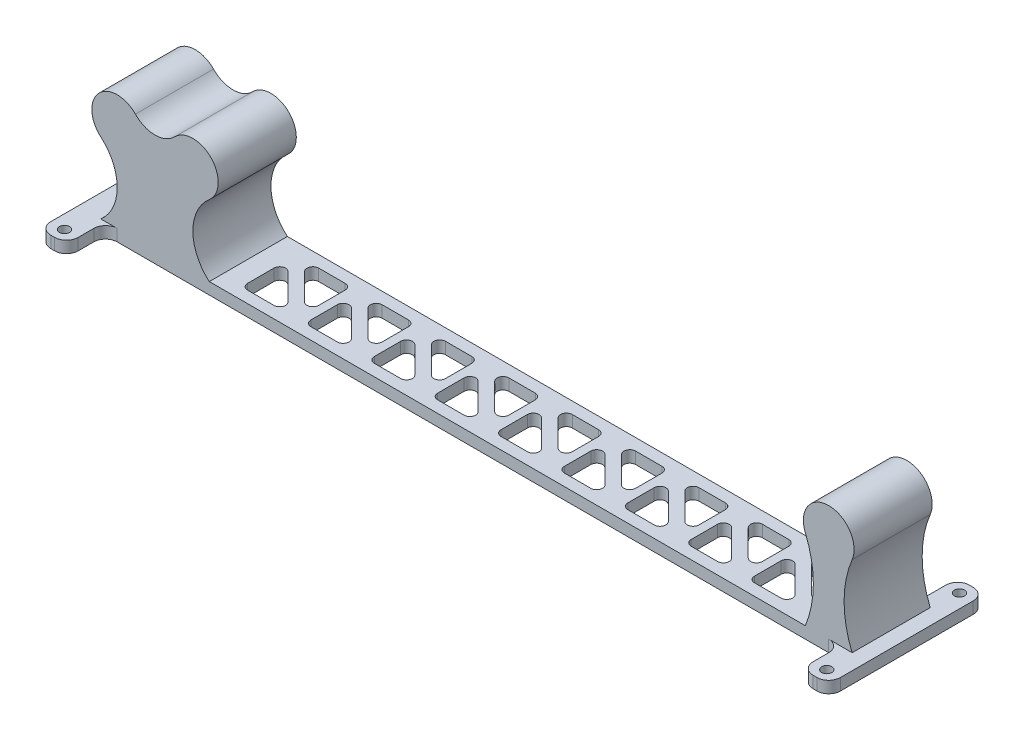
SolidWorks part; units mm, degrees
ref_plane "Front Plane" through (0, 0, 0) normal (0, 0, 1) x (1, 0, 0)
ref_plane "Top Plane" through (0, 0, 0) normal (0, 1, 0) x (1, 0, 0)
ref_plane "Right Plane" through (0, 0, 0) normal (1, 0, 0) x (0, 0, -1)
sketch "Sketch1" plane through (0, 0, 0) normal (0, 0, 1) x (1, 0, 0)
  line L0 (4.2086, -23.15) -> (156.86, -23.15)
  line L1 (-19.38, 0) -> (0, 0) construction
  line L2 (-9.69, 0) -> (-9.69, -23.15) construction
  line L3 (-23.5886, -4.9535) -> (-23.5886, -23.15) construction
  line L4 (-19.38, -14.0518) -> (-19.38, 0) construction
  line L5 (162.86, 0) -> (162.86, -23.15) construction
  line L6 (168.86, -2.5) -> (168.86, -23.15) construction
  line L7 (-29.38, -23.15) -> (-29.38, -26.15)
  line L8 (-29.38, -26.15) -> (172.86, -26.15)
  line L9 (172.86, -26.15) -> (172.86, -23.15)
  line L10 (-23.5886, -23.15) -> (-29.38, -23.15)
  line L11 (168.86, -23.15) -> (172.86, -23.15)
  circle A0 centre (0, 0) radius 3.3734
  circle A1 centre (-19.38, 0) radius 3.3734
  circle A2 centre (162.86, 0) radius 3.3734
  arc A3 (-14.7144, 4.5258) -> (-23.5886, -4.9535) centre (-19.38, 0) ccw
  arc A4 (4.2086, -4.9535) -> (-4.6656, 4.5258) centre (0, 0) ccw
  arc A5 (-23.5886, -4.9535) -> (-23.5886, -23.15) centre (-31.3186, -14.0518) cw
  arc A6 (-14.7144, 4.5258) -> (-4.6656, 4.5258) centre (-9.69, 9.3997) ccw
  arc A7 (4.2086, -4.9535) -> (4.2086, -23.15) centre (11.9386, -14.0518) ccw
  arc A8 (168.86, -2.5) -> (156.86, -2.5) centre (162.86, 0) ccw
  arc A9 (168.86, -2.5) -> (168.86, -23.15) centre (193.64, -12.825) ccw
  arc A10 (156.86, -2.5) -> (156.86, -23.15) centre (132.08, -12.825) cw
  dimension "D1" = 6.7469
  dimension "D7" = 13
  dimension "D8" = 7
  dimension "D2" = 19.38
  dimension "D3" = 162.86
  dimension "D4" = 10
  dimension "D5" = 10
  dimension "D6" = 3
  dimension "D9" = 6
  dimension "D10" = 26.15
extrude "Boss-Extrude1" add sketch "Sketch1" along normal blind 20 contours A0 | A1 | A2 | A8 A10 L0 A7 A4 A6 A3 A5 L10 L7 L8 L9 L11 A9 region at (0, 0, 0) region at (-19.38, 0, 0) region at (162.86, 0, 0)
extrude "Boss-Extrude2" add sketch "Sketch1<3>" against normal blind 3 from surface contours A8 A10 L0 A7 A4 A6 A3 A5 L10 L7 L8 L9 L11 A9 A0 A1 A2 | A0 | A1 | A2 region at (80.5343, -25.1986, 0) region at (0, 0, 0) region at (-19.38, 0, 0) region at (162.86, 0, 0) starting at face at (-16.0066, 0, 20)
sketch "Sketch1<3>" plane through (0, 0, 0) normal (0, 0, 1) x (1, 0, 0) same geometry as "Sketch1"
sketch "Sketch2" plane through (0, -23.15, 0) normal (0, 1, 0) x (1, 0, 0)
  line L0 (6.5, 0) -> (26.5, -20) construction
  line L1 (4.2086, -20) -> (156.86, -20) construction
  line L2 (9.5, -8.7426) -> (9.5, -15.5)
  line L3 (11, -17) -> (17.7574, -17)
  line L4 (18.818, -14.4393) -> (12.0607, -7.682)
  line L5 (6.5, -20) -> (6.5, 0) construction
  line L6 (23.5, -4.5) -> (23.5, -11.2574)
  line L7 (15.2426, -3) -> (22, -3)
  line L8 (20.9393, -12.318) -> (14.182, -5.5607)
  line L9 (35.0505, -14.4393) -> (28.2932, -7.682)
  line L10 (25.7325, -8.7426) -> (25.7325, -15.5)
  line L11 (27.2325, -17) -> (33.9899, -17)
  line L12 (39.7325, -4.5) -> (39.7325, -11.2574)
  line L13 (37.1718, -12.318) -> (30.4145, -5.5607)
  line L14 (31.4751, -3) -> (38.2325, -3)
  line L15 (51.283, -14.4393) -> (44.5257, -7.682)
  line L16 (41.965, -8.7426) -> (41.965, -15.5)
  line L17 (43.465, -17) -> (50.2224, -17)
  line L18 (55.965, -4.5) -> (55.965, -11.2574)
  line L19 (53.4043, -12.318) -> (46.647, -5.5607)
  line L20 (47.7076, -3) -> (54.465, -3)
  line L21 (67.5155, -14.4393) -> (60.7582, -7.682)
  line L22 (58.1975, -8.7426) -> (58.1975, -15.5)
  line L23 (59.6975, -17) -> (66.4549, -17)
  line L24 (72.1975, -4.5) -> (72.1975, -11.2574)
  line L25 (69.6368, -12.318) -> (62.8795, -5.5607)
  line L26 (63.9401, -3) -> (70.6975, -3)
  line L27 (83.748, -14.4393) -> (76.9907, -7.682)
  line L28 (74.43, -8.7426) -> (74.43, -15.5)
  line L29 (75.93, -17) -> (82.6874, -17)
  line L30 (88.43, -4.5) -> (88.43, -11.2574)
  line L31 (85.8693, -12.318) -> (79.112, -5.5607)
  line L32 (80.1726, -3) -> (86.93, -3)
  line L33 (99.9805, -14.4393) -> (93.2232, -7.682)
  line L34 (90.6625, -8.7426) -> (90.6625, -15.5)
  line L35 (92.1625, -17) -> (98.9199, -17)
  line L36 (104.6625, -4.5) -> (104.6625, -11.2574)
  line L37 (102.1018, -12.318) -> (95.3445, -5.5607)
  line L38 (96.4051, -3) -> (103.1625, -3)
  line L39 (116.213, -14.4393) -> (109.4557, -7.682)
  line L40 (106.895, -8.7426) -> (106.895, -15.5)
  line L41 (108.395, -17) -> (115.1524, -17)
  line L42 (120.895, -4.5) -> (120.895, -11.2574)
  line L43 (118.3343, -12.318) -> (111.577, -5.5607)
  line L44 (112.6376, -3) -> (119.395, -3)
  line L45 (132.4455, -14.4393) -> (125.6882, -7.682)
  line L46 (123.1275, -8.7426) -> (123.1275, -15.5)
  line L47 (124.6275, -17) -> (131.3849, -17)
  line L48 (137.1275, -4.5) -> (137.1275, -11.2574)
  line L49 (134.5668, -12.318) -> (127.8095, -5.5607)
  line L50 (128.8701, -3) -> (135.6275, -3)
  line L51 (148.678, -14.4393) -> (141.9207, -7.682)
  line L52 (139.36, -8.7426) -> (139.36, -15.5)
  line L53 (140.86, -17) -> (147.6174, -17)
  line L54 (153.36, -4.5) -> (153.36, -11.2574)
  line L55 (150.7993, -12.318) -> (144.042, -5.5607)
  line L56 (145.1026, -3) -> (151.86, -3)
  line L57 (156.36, 0) -> (156.36, -20) construction
  arc A0 (18.818, -14.4393) -> (17.7574, -17) centre (17.7574, -15.5) cw
  arc A1 (9.5, -8.7426) -> (12.0607, -7.682) centre (11, -8.7426) cw
  arc A2 (9.5, -15.5) -> (11, -17) centre (11, -15.5) ccw
  arc A3 (15.2426, -3) -> (14.182, -5.5607) centre (15.2426, -4.5) ccw
  arc A4 (23.5, -11.2574) -> (20.9393, -12.318) centre (22, -11.2574) cw
  arc A5 (22, -3) -> (23.5, -4.5) centre (22, -4.5) cw
  arc A6 (25.7325, -8.7426) -> (28.2932, -7.682) centre (27.2325, -8.7426) cw
  arc A7 (35.0505, -14.4393) -> (33.9899, -17) centre (33.9899, -15.5) cw
  arc A8 (25.7325, -15.5) -> (27.2325, -17) centre (27.2325, -15.5) ccw
  arc A9 (38.2325, -3) -> (39.7325, -4.5) centre (38.2325, -4.5) cw
  arc A10 (39.7325, -11.2574) -> (37.1718, -12.318) centre (38.2325, -11.2574) cw
  arc A11 (31.4751, -3) -> (30.4145, -5.5607) centre (31.4751, -4.5) ccw
  arc A12 (41.965, -8.7426) -> (44.5257, -7.682) centre (43.465, -8.7426) cw
  arc A13 (51.283, -14.4393) -> (50.2224, -17) centre (50.2224, -15.5) cw
  arc A14 (41.965, -15.5) -> (43.465, -17) centre (43.465, -15.5) ccw
  arc A15 (54.465, -3) -> (55.965, -4.5) centre (54.465, -4.5) cw
  arc A16 (55.965, -11.2574) -> (53.4043, -12.318) centre (54.465, -11.2574) cw
  arc A17 (47.7076, -3) -> (46.647, -5.5607) centre (47.7076, -4.5) ccw
  arc A18 (58.1975, -8.7426) -> (60.7582, -7.682) centre (59.6975, -8.7426) cw
  arc A19 (67.5155, -14.4393) -> (66.4549, -17) centre (66.4549, -15.5) cw
  arc A20 (58.1975, -15.5) -> (59.6975, -17) centre (59.6975, -15.5) ccw
  arc A21 (70.6975, -3) -> (72.1975, -4.5) centre (70.6975, -4.5) cw
  arc A22 (72.1975, -11.2574) -> (69.6368, -12.318) centre (70.6975, -11.2574) cw
  arc A23 (63.9401, -3) -> (62.8795, -5.5607) centre (63.9401, -4.5) ccw
  arc A24 (74.43, -8.7426) -> (76.9907, -7.682) centre (75.93, -8.7426) cw
  arc A25 (83.748, -14.4393) -> (82.6874, -17) centre (82.6874, -15.5) cw
  arc A26 (74.43, -15.5) -> (75.93, -17) centre (75.93, -15.5) ccw
  arc A27 (86.93, -3) -> (88.43, -4.5) centre (86.93, -4.5) cw
  arc A28 (88.43, -11.2574) -> (85.8693, -12.318) centre (86.93, -11.2574) cw
  arc A29 (80.1726, -3) -> (79.112, -5.5607) centre (80.1726, -4.5) ccw
  arc A30 (90.6625, -8.7426) -> (93.2232, -7.682) centre (92.1625, -8.7426) cw
  arc A31 (99.9805, -14.4393) -> (98.9199, -17) centre (98.9199, -15.5) cw
  arc A32 (90.6625, -15.5) -> (92.1625, -17) centre (92.1625, -15.5) ccw
  arc A33 (103.1625, -3) -> (104.6625, -4.5) centre (103.1625, -4.5) cw
  arc A34 (104.6625, -11.2574) -> (102.1018, -12.318) centre (103.1625, -11.2574) cw
  arc A35 (96.4051, -3) -> (95.3445, -5.5607) centre (96.4051, -4.5) ccw
  arc A36 (106.895, -8.7426) -> (109.4557, -7.682) centre (108.395, -8.7426) cw
  arc A37 (116.213, -14.4393) -> (115.1524, -17) centre (115.1524, -15.5) cw
  arc A38 (106.895, -15.5) -> (108.395, -17) centre (108.395, -15.5) ccw
  arc A39 (119.395, -3) -> (120.895, -4.5) centre (119.395, -4.5) cw
  arc A40 (120.895, -11.2574) -> (118.3343, -12.318) centre (119.395, -11.2574) cw
  arc A41 (112.6376, -3) -> (111.577, -5.5607) centre (112.6376, -4.5) ccw
  arc A42 (123.1275, -8.7426) -> (125.6882, -7.682) centre (124.6275, -8.7426) cw
  arc A43 (132.4455, -14.4393) -> (131.3849, -17) centre (131.3849, -15.5) cw
  arc A44 (123.1275, -15.5) -> (124.6275, -17) centre (124.6275, -15.5) ccw
  arc A45 (135.6275, -3) -> (137.1275, -4.5) centre (135.6275, -4.5) cw
  arc A46 (137.1275, -11.2574) -> (134.5668, -12.318) centre (135.6275, -11.2574) cw
  arc A47 (128.8701, -3) -> (127.8095, -5.5607) centre (128.8701, -4.5) ccw
  arc A48 (139.36, -8.7426) -> (141.9207, -7.682) centre (140.86, -8.7426) cw
  arc A49 (148.678, -14.4393) -> (147.6174, -17) centre (147.6174, -15.5) cw
  arc A50 (139.36, -15.5) -> (140.86, -17) centre (140.86, -15.5) ccw
  arc A51 (151.86, -3) -> (153.36, -4.5) centre (151.86, -4.5) cw
  arc A52 (153.36, -11.2574) -> (150.7993, -12.318) centre (151.86, -11.2574) cw
  arc A53 (145.1026, -3) -> (144.042, -5.5607) centre (145.1026, -4.5) ccw
  point P15 (21.3787, -17)
  point P18 (9.5, -5.1213)
  point P21 (9.5, -17)
  point P24 (11.6213, -3)
  point P27 (23.5, -14.8787)
  point P30 (23.5, -3)
  dimension "D5" = 1.5
  dimension "D1" = 45
  dimension "D2" = 3
  dimension "D3" = 3
  dimension "D4" = 3
  dimension "D7" = 3
  dimension "D6" = 9
extrude "Cut-Extrude1" cut sketch "Sketch2" against normal through all
sketch "Sketch3" plane through (0, -23.15, 0) normal (0, 1, 0) x (1, 0, 0)
  line L0 (-25.88, 7) -> (-25.88, 10) construction
  line L1 (-29.38, 0) -> (-22.38, 0)
  line L2 (-29.38, 0) -> (-29.38, 10)
  line L3 (-29.38, 10) -> (-22.38, 10)
  line L4 (-22.38, 0) -> (-22.38, 10)
  line L5 (-29.38, -10) -> (172.86, -10) construction
  line L6 (-29.38, -20) -> (-29.38, 0) construction
  line L7 (172.86, -20) -> (172.86, 0) construction
  line L8 (71.74, -10) -> (71.74, -20) construction
  line L9 (4.2086, -20) -> (156.86, -20) construction
  line L10 (-29.38, 0) -> (-29.38, 10)
  line L11 (-22.38, 0) -> (-22.38, 10)
  line L12 (-29.38, 0) -> (-29.38, 10)
  line L13 (-22.38, 0) -> (-22.38, 10)
  line L14 (-29.38, 0) -> (-29.38, 10)
  line L15 (-22.38, 0) -> (-22.38, 10)
  line L16 (-29.38, -30) -> (-22.38, -30)
  line L17 (-22.38, -20) -> (-22.38, -30)
  line L18 (-29.38, -20) -> (-22.38, -20)
  line L19 (-29.38, -20) -> (-29.38, -30)
  line L20 (-22.38, -20) -> (-22.38, -30)
  line L21 (-29.38, -20) -> (-29.38, -30)
  line L22 (-29.38, 0) -> (-29.38, 10)
  line L23 (-22.38, 0) -> (-22.38, 10)
  line L24 (-29.38, 0) -> (-29.38, 10)
  line L25 (-22.38, 0) -> (-22.38, 10)
  line L26 (-29.38, 0) -> (-29.38, 10)
  line L27 (-22.38, 0) -> (-22.38, 10)
  line L28 (-29.38, 0) -> (-29.38, 10)
  line L29 (-22.38, 0) -> (-22.38, 10)
  line L30 (169.36, 7) -> (169.36, 10) construction
  line L31 (165.86, 0) -> (165.86, 10)
  line L32 (172.86, 0) -> (172.86, 10)
  line L33 (165.86, 0) -> (165.86, 10)
  line L34 (172.86, 0) -> (172.86, 10)
  line L35 (165.86, 0) -> (165.86, 10)
  line L36 (172.86, 0) -> (172.86, 10)
  line L37 (165.86, 0) -> (165.86, 10)
  line L38 (172.86, 0) -> (172.86, 10)
  line L39 (172.86, -20) -> (172.86, -30)
  line L40 (165.86, -20) -> (165.86, -30)
  line L41 (172.86, -20) -> (172.86, -30)
  line L42 (172.86, -20) -> (165.86, -20)
  line L43 (165.86, -20) -> (165.86, -30)
  line L44 (172.86, -30) -> (165.86, -30)
  line L45 (165.86, 0) -> (165.86, 10)
  line L46 (172.86, 0) -> (172.86, 10)
  line L47 (165.86, 0) -> (165.86, 10)
  line L48 (172.86, 0) -> (172.86, 10)
  line L49 (165.86, 0) -> (165.86, 10)
  line L50 (172.86, 0) -> (172.86, 10)
  line L51 (165.86, 0) -> (165.86, 10)
  line L52 (172.86, 10) -> (165.86, 10)
  line L53 (172.86, 0) -> (172.86, 10)
  line L54 (172.86, 0) -> (165.86, 0)
  circle A0 centre (-25.88, 7) radius 1.3
  circle A1 centre (-25.88, -27) radius 1.3
  circle A2 centre (169.36, -27) radius 1.3
  circle A3 centre (169.36, 7) radius 1.3
  dimension "D3" = 2.6
  dimension "D1" = 7
  dimension "D2" = 10
  dimension "D4" = 7
extrude "Boss-Extrude3" add sketch "Sketch3" against normal blind 3 contours L18 L19 L16 L17 A1 | L1 L4 L3 L2 A0 | L44 L39 L42 L40 A2 | L54 L32 L52 L31 A3 region at (-25.88, -23.15, -4.8359) region at (-25.88, -23.15, 24.8359) region at (169.36, -23.15, -4.8359) region at (169.36, -23.15, 24.8359)
fillet "Fillet1" radius 3 12 edges at (172.86, -24.65, 30) (165.86, -24.65, 30) (165.86, -24.65, 20) (165.86, -24.65, 0) (165.86, -24.65, -10) (172.86, -24.65, -10) (-22.38, -24.65, 0) (-22.38, -24.65, 20) (-22.38, -24.65, 30) (-29.38, -24.65, 30) (-22.38, -24.65, -10) (-29.38, -24.65, -10)
